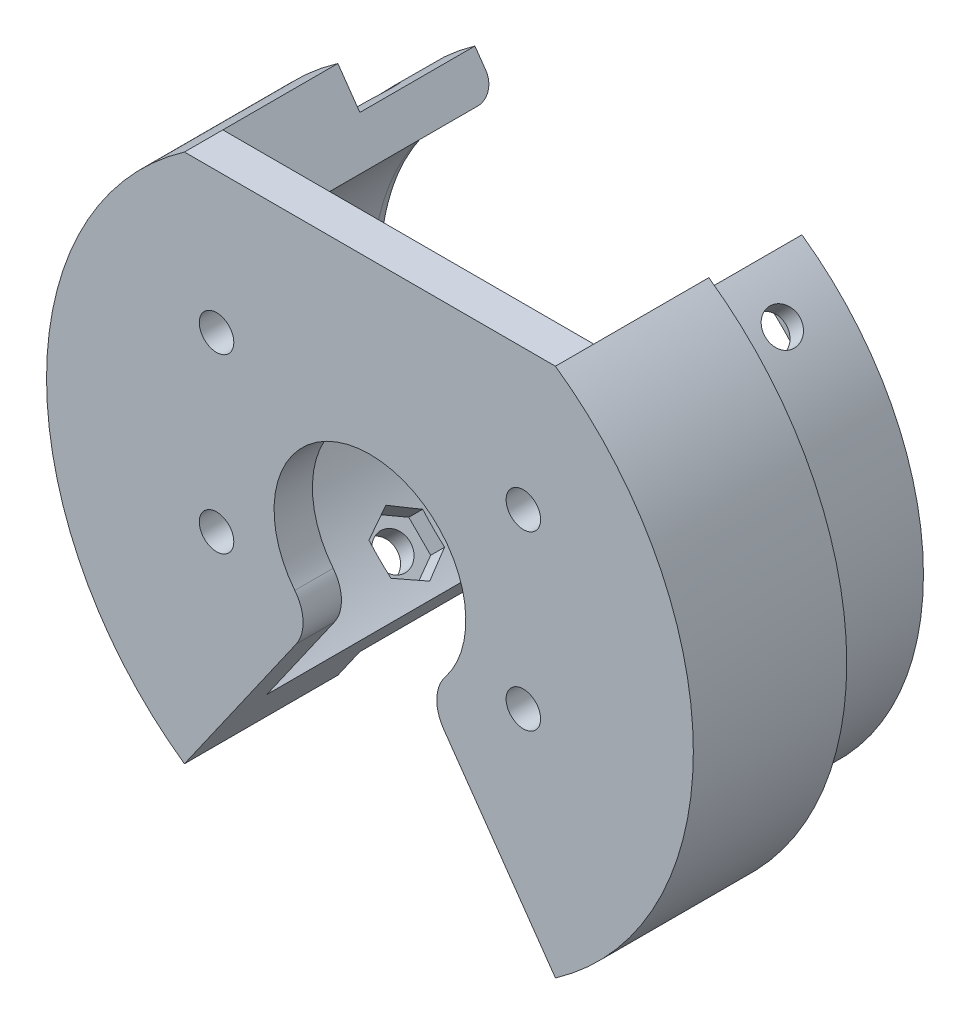
SolidWorks part; units mm, degrees
ref_plane "Front Plane" through (0, 0, 0) normal (0, 0, 1) x (1, 0, 0)
ref_plane "Top Plane" through (0, 0, 0) normal (0, 1, 0) x (1, 0, 0)
ref_plane "Right Plane" through (0, 0, 0) normal (1, 0, 0) x (0, 0, -1)
sketch "Sketch1" plane through (0, 0, 0) normal (0, 0, 1) x (1, 0, 0)
  line L0 (0, 32.1622) -> (0, 37.1622) construction
  circle A0 centre (0, 0) radius 37.1622
  circle A1 centre (0, 0) radius 32.1622
  dimension "D1" = 74.3245
  dimension "D2" = 5
extrude "Boss-Extrude1" add sketch "Sketch1" along normal mid plane 15
sketch "Sketch2" plane through (0, 0, 0) normal (0, 0, 1) x (1, 0, 0)
  line L0 (0, 0) -> (-21.3154, 30.4415) construction
  line L1 (0, 0) -> (0, 37.1622) construction
  line L2 (0, 0) -> (21.3154, 30.4415) construction
  line L3 (21.3154, 30.4415) -> (18.4475, 26.3458)
  line L4 (-18.4475, 26.3458) -> (-21.3154, 30.4415)
  circle A0 centre (0, 0) radius 37.1622 construction
  arc A1 (-18.4475, 26.3458) -> (18.4475, 26.3458) centre (0, 0) cw
  circle A2 centre (0, 0) radius 32.1622 construction
  arc A3 (-21.3154, 30.4415) -> (21.3154, 30.4415) centre (0, 0) cw
  dimension "D1" = 70
extrude "Cut-Extrude1" cut sketch "Sketch2" against normal through all both and the other way through all
mirror "Mirror1" about plane through (0, 0, 0) normal (0, 1, 0) of "Cut-Extrude1"
sketch "Sketch3" plane through (0, 0, 7.5) normal (0, 0, 1) x (1, 0, 0)
  line L0 (-18.4475, 26.3458) -> (-24.1833, 34.5373)
  line L1 (-18.4475, -26.3458) -> (-24.1833, -34.5373)
  line L2 (-21.3154, 30.4415) -> (-18.4475, 26.3458) construction
  line L3 (-21.3154, -30.4415) -> (-18.4475, -26.3458) construction
  line L4 (0, 0) -> (0, 26.3458) construction
  line L5 (18.4475, -26.3458) -> (24.1833, -34.5373)
  line L6 (18.4475, 26.3458) -> (24.1833, 34.5373)
  arc A0 (-18.4475, 26.3458) -> (-18.4475, -26.3458) centre (0, 0) ccw construction
  arc A1 (-18.4475, 26.3458) -> (-18.4475, -26.3458) centre (0, 0) ccw
  arc A2 (-24.1833, -34.5373) -> (-24.1833, 34.5373) centre (0, 0) cw
  arc A3 (24.1833, -34.5373) -> (24.1833, 34.5373) centre (0, 0) ccw
  arc A4 (18.4475, 26.3458) -> (18.4475, -26.3458) centre (0, 0) cw
  dimension "D1" = 10
extrude "Boss-Extrude2" add sketch "Sketch3" along normal blind 15
sketch "Sketch4" plane through (0, 0, 22.5) normal (0, 0, 1) x (1, 0, 0)
  line L0 (24.1833, 34.5373) -> (-24.1833, 34.5373)
  line L1 (24.1833, -34.5373) -> (-24.1833, -34.5373)
  circle A0 centre (0, 0) radius 42.1622 construction
  arc A1 (24.1833, -34.5373) -> (24.1833, 34.5373) centre (0, 0) ccw construction
  arc A2 (-24.1833, -34.5373) -> (-24.1833, 34.5373) centre (0, 0) cw
  arc A3 (24.1833, 34.5373) -> (24.1833, -34.5373) centre (0, 0) cw
extrude "Boss-Extrude3" add sketch "Sketch4" along normal blind 5
ref_plane "Plane1" through (0, 0, 0) normal (0, 0, -1) x (-1, 0, 0)
sketch "Sketch7" plane through (0, 0, 0) normal (0, 0, -1) x (-1, 0, 0)
  line L0 (0, 0) -> (-42.1622, 0) construction
  line L2 (0, 0) -> (-22.7421, 22.7421) construction
  arc A0 (-24.1833, 34.5373) -> (-24.1833, -34.5373) centre (0, 0) ccw construction
  arc A1 (-18.4475, 26.3458) -> (-18.4475, -26.3458) centre (0, 0) ccw construction
  dimension "D1" = 45
ref_plane "Plane3" through (22.7421, 22.7421, 0) normal (0.7071, 0.7071, 0) x (0.7071, -0.7071, 0)
sketch "Sketch8" plane through (22.7421, 22.7421, 0) normal (0.7071, 0.7071, 0) x (0.7071, -0.7071, 0)
  circle A0 centre (0, 0) radius 2.25
  dimension "D1" = 4.5
extrude "Cut-Extrude2" cut sketch "Sketch8" along normal through all and the other way blind 10
sketch "Sketch9" plane through (22.7421, 22.7421, 0) normal (0.7071, 0.7071, 0) x (0.7071, -0.7071, 0)
  line L1 (2.0207, -3.5) -> (4.0415, 0)
  line L2 (4.0415, 0) -> (2.0207, 3.5)
  line L3 (2.0207, 3.5) -> (-2.0207, 3.5)
  line L4 (-2.0207, 3.5) -> (-4.0415, 0)
  line L5 (-4.0415, 0) -> (-2.0207, -3.5)
  line L6 (-2.0207, -3.5) -> (2.0207, -3.5)
  circle A0 centre (0, 0) radius 3.5 construction
  dimension "D1" = 7
extrude "Cut-Extrude3" cut sketch "Sketch9" along normal blind 2.5 and the other way blind 10
mirror "Mirror2" about plane through (0, 0, 0) normal (0, 1, 0) of "Cut-Extrude3", "Cut-Extrude2"
mirror "Mirror3" about plane through (0, 0, 0) normal (1, 0, 0) of "Mirror2"
sketch "Sketch10" plane through (0, 0, 27.5) normal (0, 0, 1) x (1, 0, 0)
  line L0 (-24.1833, -34.5373) -> (-7.1697, -10.2394)
  line L1 (-24.1833, -34.5373) -> (-18.4475, -26.3458) construction
  line L2 (0, 0) -> (0, -34.5373) construction
  line L3 (-24.1833, -34.5373) -> (24.1833, -34.5373) construction
  line L4 (24.1833, -34.5373) -> (7.1697, -10.2394)
  line L5 (-24.1833, -34.5373) -> (24.1833, -34.5373)
  circle A0 centre (0, 0) radius 12.5 construction
  arc A1 (-7.1697, -10.2394) -> (7.1697, -10.2394) centre (0, 0) cw
  dimension "D1" = 25
extrude "Cut-Extrude4" cut sketch "Sketch10" against normal through all both and the other way through all
fillet "Fillet1" radius 5 2 edges at (7.1697, -10.2394, 25) (-7.1697, -10.2394, 25)
fillet "Fillet2" radius 2.5 2 edges at (32.1622, 0, -7.5) (-32.1622, 0, -7.5)
sketch "Sketch11" plane through (0, 0, 27.5) normal (0, 0, 1) x (1, 0, 0)
  line L1 (-20, -6.25) -> (20, -6.25) construction
  line L2 (-20, -6.25) -> (-20, 16.25) construction
  line L3 (-20, 16.25) -> (20, 16.25) construction
  line L4 (20, -6.25) -> (20, 16.25) construction
  line L5 (0, 16.25) -> (0, -6.25) construction
  line L6 (-20, 5) -> (20, 5) construction
  circle A0 centre (-20, -6.25) radius 2.25
  circle A1 centre (-20, 16.25) radius 2.25
  circle A2 centre (20, 16.25) radius 2.25
  circle A3 centre (20, -6.25) radius 2.25
  point P0 (0, 0)
  dimension "D1" = 4.5
  dimension "D2" = 0
  dimension "D3" = 5
  dimension "D4" = 22.5
  dimension "D5" = 40
extrude "example_mount" cut sketch "Sketch11" against normal through all
